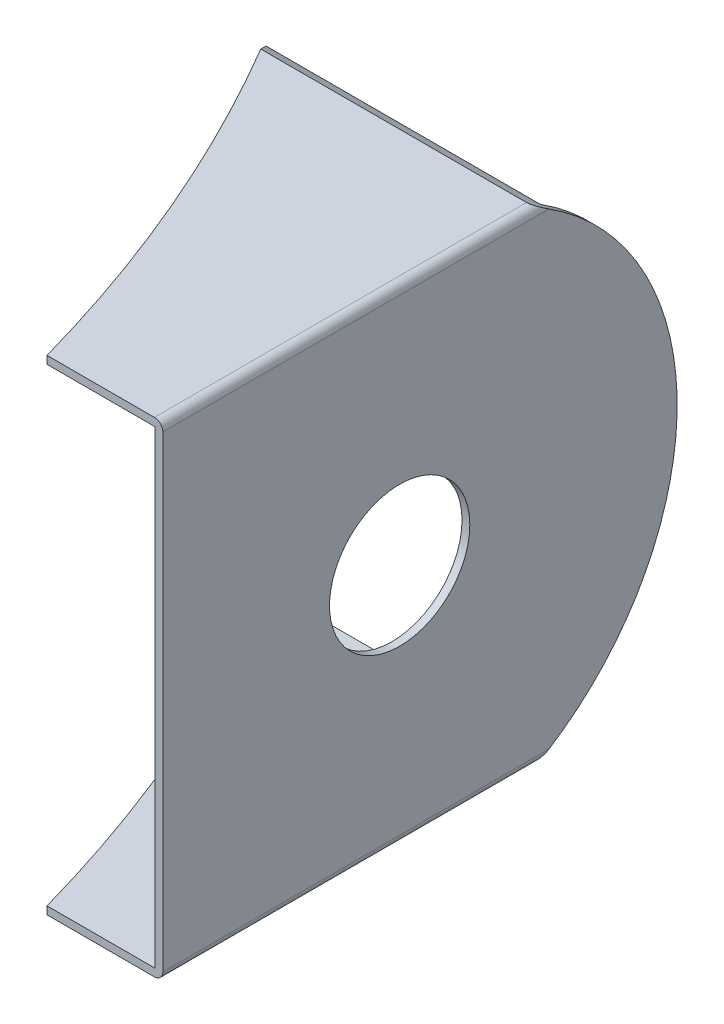
SolidWorks part; units mm, degrees
note: The reader was unsure of these and kept them because the rebuilt part matched: flange length of "Edge-Flange1".
material "ASTM A36 Steel"
ref_plane "Front Plane" through (0, 0, 0) normal (0, 0, 1) x (1, 0, 0)
ref_plane "Top Plane" through (0, 0, 0) normal (0, 1, 0) x (1, 0, 0)
ref_plane "Right Plane" through (0, 0, 0) normal (1, 0, 0) x (0, 0, -1)
sketch "Sketch1" plane through (0, 0, 0) normal (1, 0, 0) x (0, 0, -1)
  line L1 (-365, -75) -> (365, -75)
  line L2 (-365, -75) -> (-365, 75)
  line L3 (-365, 75) -> (365, 75)
  line L4 (365, -75) -> (365, 75)
  line L5 (-365, -75) -> (365, 75) construction
  line L6 (-365, 75) -> (365, -75) construction
  point P0 (0, 0)
  dimension "D1" = 150
  dimension "D2" = 730
base flange "Base-Flange1" sketch "Sketch1" thickness 2.5 reverse thickness direction no parameters "D1"=0.2
edge flange "Edge-Flange1" sketch "Sketch10" flange profiles "Sketch10", "Sketch11" flange angle 90 flange length 130 flange position bend outside bend radius 0.2 thickness 2.5 relief rectangular parameters "D6"=10, "D8"=1
sketch "Sketch10" plane through (-2.5, 75, 0) normal (0, -1, 0) x (0, 0, 1)
  line L2 (-365, 0) -> (-365, 127.5)
  line L3 (-365, 127.5) -> (365, 127.5)
  line L4 (365, 127.5) -> (365, 0)
  line L5 (365, 0) -> (-365, 0) construction
  line L6 (365, 0) -> (-365, 0)
sketch "Sketch11" plane through (-2.5, -75, 0) normal (0, 1, 0) x (0, 0, -1)
  line L0 (365, 0) -> (-365, 0) construction
  line L1 (365, 0) -> (-365, 0)
  line L2 (365, 0) -> (365, 127.5)
  line L3 (365, 127.5) -> (-365, 127.5)
  line L4 (-365, 127.5) -> (-365, 0)
bend "EdgeBend1" bend radius 0.2 bend angle 90 parameters "D5"=1
bend "EdgeBend2" bend radius 0.2 bend angle 90 parameters "D5"=2
sketch "Sketch12" plane through (0, 77.7, 0) normal (0, 1, 0) x (1, 0, 0)
  line L1 (-130, 365) -> (-2.7, 365) construction
  line L2 (-130, -365) -> (-130, 365) construction
  circle A0 centre (-530, 54) radius 501.5
  dimension "D1" = 1003
  dimension "D3" = 400
  dimension "D2" = 311
sketch "Sketch13" plane through (0, 0, 0) normal (1, 0, 0) x (0, 0, -1)
  line L0 (365, -75) -> (365, 75) construction
  line L1 (-365, 75) -> (-365, -75) construction
  circle A0 centre (265, 0) radius 22.5
  circle A1 centre (-290, 0) radius 22.5
  dimension "D1" = 45
  dimension "D2" = 100
  dimension "D3" = 45
  dimension "D4" = 75
extrude "Cut-Extrude2" cut sketch "Sketch13" against normal blind 10
sketch "Sketch14" plane through (0, 0, 0) normal (1, 0, 0) x (0, 0, -1)
  line L1 (189.0395, 122.5591) -> (-442.2981, 122.5591)
  line L2 (189.0395, 122.5591) -> (189.0395, -150.5984)
  line L3 (189.0395, -150.5984) -> (-442.2981, -150.5984)
  line L4 (-442.2981, 122.5591) -> (-442.2981, -150.5984)
extrude "Cut-Extrude3" cut sketch "Sketch14" against normal through all both and the other way through all
sketch "Sketch15" plane through (0, 0, 0) normal (1, 0, 0) x (0, 0, -1)
  line L0 (302.2666, 80.8221) -> (310.532, 105.3518)
  line L1 (310.532, 105.3518) -> (400.6684, 94.5662)
  line L2 (400.6684, 94.5662) -> (380.2529, -108.0482)
  line L3 (380.2529, -108.0482) -> (291.2869, -85.0294)
  arc A0 (291.2869, -85.0294) -> (302.2666, 80.8221) centre (265, 0) ccw
  dimension "D1" = 178
extrude "Cut-Extrude4" cut sketch "Sketch15" against normal through all both and the other way through all
sketch "Sketch17" plane through (0, 77.7, 0) normal (0, 1, 0) x (1, 0, 0)
  line L0 (-118.8192, 354.7515) -> (-213.8379, 354.7515)
  line L1 (-213.8379, 354.7515) -> (-213.8379, 158.3804)
  line L2 (-213.8379, 158.3804) -> (-29.6136, 158.3804)
  circle A0 centre (-520.1306, 54) radius 501.5 construction
  arc A1 (-29.6136, 158.3804) -> (-118.8192, 354.7515) centre (-520.1306, 54) ccw
extrude "Cut-Extrude5" cut sketch "Sketch17" against normal through all normal cut yes
sketch "Bend-Lines1" [suppressed] plane through (0, 0, 0) normal (0, 1, 0) x (1, 0, 0)
sketch "Bounding-Box1" [suppressed] plane through (0, 0, 0) normal (0, 1, 0) x (1, 0, 0)
sheet metal parameters "Sheet-Metal1" thickness 2.5 parameters "D1"=0.2
flat pattern "Flat-Pattern1" [suppressed]
sketch "Bend-Lines2" plane through (0, 0, 0) normal (0, 1, 0) x (1, 0, 0)
sketch3d "Bounding-Box2" [suppressed]
  line L0 (-227, -60, 0) -> (227, -60, 0) construction
  line L1 (-227, 60, 0) -> (227, 60, 0) construction
  line L2 (-227, -60, 0) -> (-227, 60, 0) construction
  line L3 (227, -60, 0) -> (227, 60, 0) construction
sheet metal parameters "Sheet-Metal2" thickness 2.5 parameters "D1"=0.2
flat pattern "Flat-Pattern1"
sketch "Bend-Lines2" plane through (0, 0, 0) normal (1, 0, 0) x (0, 0, -1)
  line L0 (-227, -61.1388) -> (227, -61.1388) construction
  line L1 (227, 61.1388) -> (-227, 61.1388) construction
  line L2 (-227, -61.1388) -> (227, -61.1388) construction
  line L3 (227, 61.1388) -> (-227, 61.1388) construction
sketch3d "Bounding-Box2" [suppressed]
  line L0 (227, -139.5777, 0) -> (-227, -139.5777, 0) construction
  line L1 (227, 139.5777, 0) -> (-227, 139.5777, 0) construction
  line L2 (227, -139.5777, 0) -> (227, 139.5777, 0) construction
  line L3 (-227, -139.5777, 0) -> (-227, 139.5777, 0) construction
bend of the flat pattern "Flatten-<EdgeBend1>1"
bend of the flat pattern "Flatten-<EdgeBend2>1"
sheet metal parameters "Sheet-Metal4" thickness 2.5 parameters "D1"=0.2
flat pattern "Flat-Pattern1"
sketch "Bend-Lines2" plane through (0, 0, 0) normal (1, 0, 0) x (0, 0, -1)
  line L0 (-340, -61.1388) -> (340, -61.1388) construction
  line L1 (340, 61.1388) -> (-340, 61.1388) construction
  line L2 (-340, -61.1388) -> (340, -61.1388) construction
  line L3 (340, 61.1388) -> (-340, 61.1388) construction
sketch3d "Bounding-Box2" [suppressed]
  line L0 (340, -177.6863, 0) -> (-340, -177.6863, 0) construction
  line L1 (340, 177.6863, 0) -> (-340, 177.6863, 0) construction
  line L2 (340, -177.6863, 0) -> (340, 177.6863, 0) construction
  line L3 (-340, -177.6863, 0) -> (-340, 177.6863, 0) construction
bend of the flat pattern "Flatten-<EdgeBend1>1"
bend of the flat pattern "Flatten-<EdgeBend2>1"
sheet metal parameters "Sheet-Metal7" thickness 2.5 parameters "D1"=0.2
flat pattern "Flat-Pattern1"
sketch "Bend-Lines2" plane through (0, 0, 0) normal (1, 0, 0) x (0, 0, -1)
  line L0 (189.0395, -76.1388) -> (365, -76.1388) construction
  line L1 (365, 76.1388) -> (189.0395, 76.1388) construction
  line L2 (189.0395, -76.1388) -> (365, -76.1388) construction
  line L3 (365, 76.1388) -> (189.0395, 76.1388) construction
sketch3d "Bounding-Box2" [suppressed]
  line L0 (189.0395, 204.5777, 0) -> (189.0395, -204.5777, 0) construction
  line L1 (365, 204.5777, 0) -> (365, -204.5777, 0) construction
  line L2 (189.0395, 204.5777, 0) -> (365, 204.5777, 0) construction
  line L3 (189.0395, -204.5777, 0) -> (365, -204.5777, 0) construction
bend of the flat pattern "Flatten-<EdgeBend1>1"
bend of the flat pattern "Flatten-<EdgeBend2>1"
sheet metal parameters "Sheet-Metal8" thickness 2.5 parameters "D1"=0.2
flat pattern "Flat-Pattern1" [suppressed]
sketch "Bend-Lines2" plane through (0, 0, 0) normal (1, 0, 0) x (0, 0, -1)
  line L0 (312.7593, -76.1388) -> (189.0395, -76.1388) construction
  line L1 (308.559, 76.1388) -> (189.0395, 76.1388) construction
  line L2 (312.7593, -76.1388) -> (189.0395, -76.1388) construction
  line L3 (308.559, 76.1388) -> (189.0395, 76.1388) construction
sketch3d "Bounding-Box2" [suppressed]
  line L0 (189.0395, -204.5777, 0) -> (189.0395, 204.5777, 0) construction
  line L1 (354, -204.5777, 0) -> (354, 204.5777, 0) construction
  line L2 (189.0395, -204.5777, 0) -> (354, -204.5777, 0) construction
  line L3 (189.0395, 204.5777, 0) -> (354, 204.5777, 0) construction
bend of the flat pattern "Flatten-<EdgeBend1>1"
bend of the flat pattern "Flatten-<EdgeBend2>1"
sketch "Sketch12-1" [suppressed] plane through (0, 74.5777, 0) normal (1, 0, 0) x (0, -1, 0)
  line L1 (-130, 365) -> (-2.7, 365) construction
  line L2 (-130, 189.0395) -> (-130, 308.4017) construction
  circle A0 centre (-530, 54) radius 501.5
  dimension "D1" = 1003
  dimension "D3" = 400
  dimension "D2" = 311
sheet metal parameters "Sheet-Metal11" thickness 2.5 parameters "D1"=0.2
flat pattern "Flat-Pattern1" [suppressed]
sketch "Bend-Lines2" plane through (0, 0, 0) normal (1, 0, 0) x (0, 0, -1)
  line L0 (312.7593, -76.1388) -> (189.0395, -76.1388) construction
  line L1 (308.559, 76.1388) -> (189.0395, 76.1388) construction
  line L2 (312.7593, -76.1388) -> (189.0395, -76.1388) construction
  line L3 (308.559, 76.1388) -> (189.0395, 76.1388) construction
sketch3d "Bounding-Box2" [suppressed]
  line L0 (189.0395, 162.5254, 0) -> (189.0395, -162.5254, 0) construction
  line L1 (354, 162.5254, 0) -> (354, -162.5254, 0) construction
  line L2 (189.0395, 162.5254, 0) -> (354, 162.5254, 0) construction
  line L3 (189.0395, -162.5254, 0) -> (354, -162.5254, 0) construction
bend of the flat pattern "Flatten-<EdgeBend1>1"
bend of the flat pattern "Flatten-<EdgeBend2>1"
sketch "Sketch12-1" [suppressed] plane through (0, 74.5777, 0) normal (1, 0, 0) x (0, -1, 0)
  line L1 (-130, 365) -> (-2.7, 365) construction
  line L2 (-130, -365) -> (-130, 365) construction
  circle A0 centre (-530, 54) radius 501.5
  dimension "D1" = 1003
  dimension "D3" = 400
  dimension "D2" = 311
